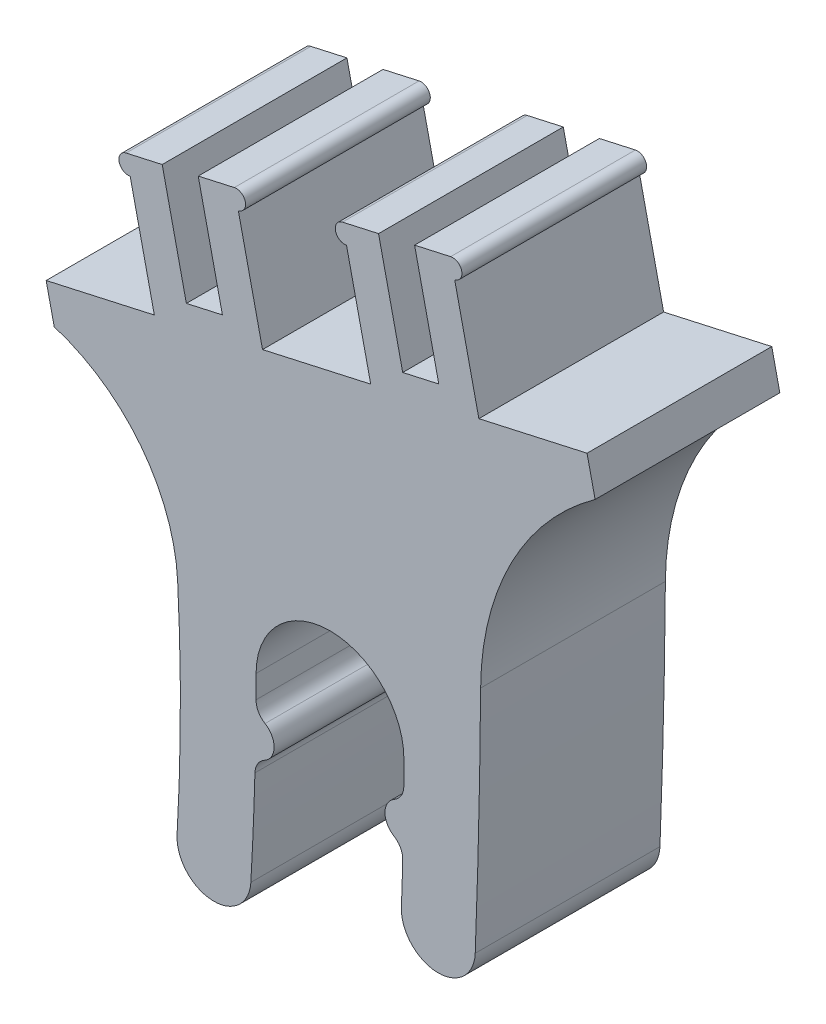
SolidWorks part; units mm, degrees
ref_plane "Front Plane" through (0, 0, 0) normal (0, 0, 1) x (1, 0, 0)
ref_plane "Top Plane" through (0, 0, 0) normal (0, 1, 0) x (1, 0, 0)
ref_plane "Right Plane" through (0, 0, 0) normal (1, 0, 0) x (0, 0, -1)
sketch "Sketch1" plane through (0, 0, 0) normal (0, 0, 1) x (1, 0, 0)
  line L0 (46.3286, 67.6651) -> (48.3537, 68.1177)
  line L1 (40.1568, 79.6066) -> (48.0305, 81.3661)
  line L3 (40.2311, 66.3025) -> (42.2676, 66.7576)
  arc A0 (46.4563, 72.4818) -> (46.4506, 71.4651) centre (-44.4563, 72.4818) cw
  arc A1 (46.4563, 72.4818) -> (42.4563, 72.4818) centre (44.4563, 72.4818) ccw
  arc A3 (42.2676, 66.7576) -> (42.4337, 70.4989) centre (-44.4563, 72.4818) ccw
  arc A4 (48.0305, 81.3661) -> (48.3537, 68.1177) centre (-44.4563, 72.4818) cw
  arc A5 (40.2311, 66.3025) -> (40.1568, 79.6066) centre (-44.4563, 72.4818) ccw
  arc A6 (48.0305, 81.3661) -> (48.1264, 64.6591) centre (-44.4563, 72.4818) cw construction
  arc A7 (46.0397, 81.1749) -> (46.1335, 64.8275) centre (-44.4563, 72.4818) cw construction
  arc A8 (42.2258, 66.157) -> (42.1498, 79.7744) centre (-44.4563, 72.4818) ccw construction
  circle A9 centre (44.4563, 72.4818) radius 2 construction
  arc A10 (42.4507, 71.4988) -> (42.4337, 70.4989) centre (42.4436, 70.9988) cw
  arc A11 (46.4506, 71.4651) -> (46.4339, 70.4652) centre (46.4436, 70.9651) ccw
  arc A12 (42.4507, 71.4988) -> (42.4563, 72.4818) centre (-44.4563, 72.4818) ccw
  arc A13 (46.4339, 70.4652) -> (46.3286, 67.6651) centre (-44.4563, 72.4818) cw
  dimension "D1" = 4
  dimension "D5" = 0.5
  dimension "D2" = 13
  dimension "D3" = 2
  dimension "D4" = 2
extrude "Boss-Extrude1" add sketch "Sketch1" along normal blind 5
fillet "Fillet1" radius 0.5 4 edges at (46.4339, 70.4652, 2.5) (46.4506, 71.4651, 2.5) (42.4337, 70.4989, 2.5) (42.4507, 71.4988, 2.5)
fillet "Fillet2" radius 1 4 edges at (48.3537, 68.1177, 2.5) (46.3286, 67.6651, 2.5) (42.2676, 66.7576, 2.5) (40.2311, 66.3025, 2.5)
sketch "Sketch2" plane through (0, 0, 5) normal (0, 0, 1) x (1, 0, 0)
  line L1 (39.702, 79.5049) -> (39.0477, 82.4327)
  line L2 (42.831, 79.259) -> (41.9755, 83.087)
  line L3 (39.0477, 82.4327) -> (41.9755, 83.087)
  line L5 (48.4854, 81.4678) -> (47.8311, 84.3955)
  line L6 (45.7587, 79.9133) -> (44.9033, 83.7413)
  line L7 (47.8311, 84.3955) -> (44.9033, 83.7413)
  line L8 (48.0305, 81.3661) -> (40.1568, 79.6066) construction
  line L9 (41.9755, 83.087) -> (44.9033, 83.7413) construction
  line L10 (44.9033, 83.7413) -> (44.9146, 83.723) construction
  line L11 (43.4394, 83.4141) -> (44.0937, 80.4863) construction
  line L12 (42.831, 79.259) -> (40.3174, 67.6268)
  line L13 (45.7587, 79.9133) -> (48.3867, 68.8877)
  arc A0 (40.3174, 67.6268) -> (39.702, 79.5049) centre (-14.2779, 70.7535) ccw
  arc A1 (48.4854, 81.4678) -> (48.3867, 68.8877) centre (-155.3783, 76.7758) cw
  arc A2 (40.3174, 67.6268) -> (40.1568, 79.6066) centre (-44.4563, 72.4818) ccw construction
  arc A3 (48.3867, 68.8877) -> (48.0305, 81.3661) centre (-44.4563, 72.4818) ccw construction
  dimension "D1" = 3
  dimension "D2" = 3
  dimension "D3" = 3
extrude "Boss-Extrude2" add sketch "Sketch2" against normal blind 5
sketch "Sketch3" plane through (0, 0, 5) normal (0, 0, 1) x (1, 0, 0)
  line L0 (38.9387, 82.9207) -> (41.8665, 83.575)
  line L1 (41.9755, 83.087) -> (39.0477, 82.4327) construction
  line L2 (38.9932, 82.6767) -> (41.921, 83.331) construction
  line L3 (44.0937, 80.4863) -> (42.4588, 87.8022) construction
  line L4 (38.9387, 82.9207) -> (39.0477, 82.4327) construction
  line L5 (41.8665, 83.575) -> (41.9755, 83.087) construction
  line L7 (45.5576, 80.8135) -> (42.6298, 80.1592) construction
  line L8 (44.7943, 84.2292) -> (44.9033, 83.7413) construction
  line L9 (47.7221, 84.8835) -> (47.8311, 84.3955) construction
  line L10 (47.7766, 84.6395) -> (44.8488, 83.9853) construction
  line L11 (47.7221, 84.8835) -> (44.7943, 84.2292)
  arc A0 (38.9387, 82.9207) -> (39.0477, 82.4327) centre (38.9932, 82.6767) ccw
  arc A1 (41.8665, 83.575) -> (41.9755, 83.087) centre (41.921, 83.331) cw
  arc A2 (44.7943, 84.2292) -> (44.9033, 83.7413) centre (44.8488, 83.9853) ccw
  arc A3 (47.7221, 84.8835) -> (47.8311, 84.3955) centre (47.7766, 84.6395) cw
  point P11 (44.0937, 80.4863)
  line M4 (47.8311, 84.3955) -> (44.9033, 83.7413)
  line M8 (41.9755, 83.087) -> (39.0477, 82.4327)
  dimension "D1" = 0.5
extrude "Boss-Extrude3" add sketch "Sketch3" against normal blind 5 contours A1 L0 A0 M8 | A3 L11 A2 M4 region at (40.4571, 83.0038, 5) region at (46.3127, 84.3124, 5)
sketch "Sketch4" plane through (0, 0, 5) normal (0, 0, 1) x (1, 0, 0)
  line L0 (39.9146, 83.1388) -> (40.5689, 80.211)
  line L1 (44.0937, 80.4863) -> (-10860.396, 48876.9217) construction
  line L2 (40.5689, 80.211) -> (41.5448, 80.4291)
  line L3 (40.8906, 83.3569) -> (41.5448, 80.4291)
  line L4 (40.4026, 83.2478) -> (41.5448, 80.4291) construction
  line L5 (40.5689, 80.211) -> (40.4026, 83.2478) construction
  line L6 (38.9387, 82.9207) -> (41.8665, 83.575) construction
  line L7 (39.9146, 83.1388) -> (40.8906, 83.3569)
  line L8 (45.5576, 80.8135) -> (42.6298, 80.1592) construction
  line L9 (47.4004, 81.7376) -> (46.2582, 84.5564) construction
  line L10 (46.2582, 84.5564) -> (46.4245, 81.5195) construction
  line L11 (46.7461, 84.6654) -> (45.7702, 84.4473)
  line L12 (45.7702, 84.4473) -> (46.4245, 81.5195)
  line L13 (47.4004, 81.7376) -> (46.4245, 81.5195)
  line L14 (46.7461, 84.6654) -> (47.4004, 81.7376)
  line L15 (40.4026, 83.2478) -> (41.0569, 80.32) construction
  point P1 (40.4026, 83.2478)
  point P12 (44.0937, 80.4863)
  dimension "D1" = 1
  dimension "D2" = 3
extrude "Cut-Extrude1" cut sketch "Sketch4" against normal blind 5
sketch "Sketch5" plane through (0, 0, 5) normal (0, 0, 1) x (1, 0, 0)
  line L0 (39.702, 79.5049) -> (36.7742, 78.8507)
  line L1 (48.4854, 81.4678) -> (51.4132, 82.122)
  line L2 (45.5576, 80.8135) -> (42.6298, 80.1592) construction
  line L3 (40.3336, 73.5826) -> (44.7739, 75.8239)
  line L4 (44.7739, 75.8239) -> (48.5331, 75.177)
  line L5 (48.4854, 81.4678) -> (45.1093, 79.7636)
  line L6 (45.1093, 79.7636) -> (39.702, 79.5049)
  line L7 (36.7742, 78.8507) -> (36.9923, 77.8747)
  line L8 (51.6312, 81.1461) -> (51.4132, 82.122)
  arc A0 (40.3336, 73.5826) -> (36.9923, 77.8747) centre (35.5905, 73.3369) ccw
  arc A1 (40.3174, 67.6268) -> (39.702, 79.5049) centre (-14.2779, 70.7535) ccw construction
  arc A2 (48.5331, 75.177) -> (51.6312, 81.1461) centre (55.9443, 75.1189) cw
  arc A3 (48.3867, 68.8877) -> (48.4854, 81.4678) centre (-155.3783, 76.7758) ccw construction
  dimension "D1" = 1
extrude "Boss-Extrude4" add sketch "Sketch5" against normal blind 5
